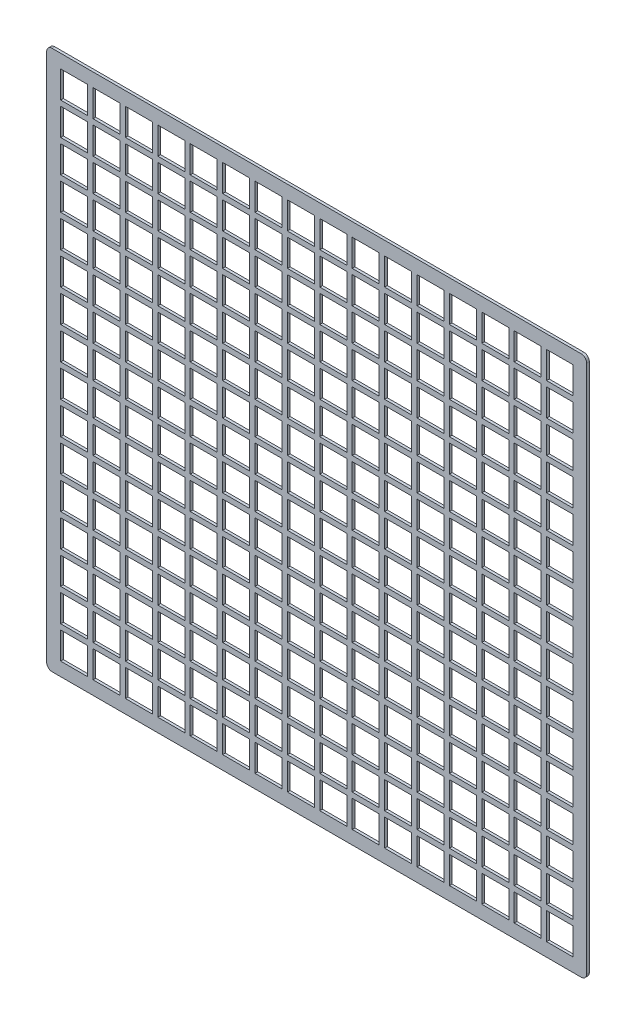
SolidWorks part; units mm, degrees
ref_plane "Front Plane" through (0, 0, 0) normal (0, 0, 1) x (1, 0, 0)
ref_plane "Top Plane" through (0, 0, 0) normal (0, 1, 0) x (1, 0, 0)
ref_plane "Right Plane" through (0, 0, 0) normal (1, 0, 0) x (0, 0, -1)
sketch "Model" plane through (0, 0, 0) normal (0, 0, 1) x (1, 0, 0)
  line L0 (0.1, 0) -> (9.9, 0)
  line L1 (10, 0.1) -> (10, 9.9)
  line L2 (9.9, 10) -> (0.1, 10)
  line L3 (0, 9.9) -> (0, 0.1)
  line L4 (0.2586, 0.25) -> (0.7586, 0.25)
  line L5 (0.7586, 0.25) -> (0.7586, 0.7491)
  line L6 (0.7586, 0.7491) -> (0.2586, 0.7491)
  line L7 (0.2586, 0.7491) -> (0.2586, 0.25)
  line L8 (0.2586, 0.8491) -> (0.7586, 0.8491)
  line L9 (0.7586, 0.8491) -> (0.7586, 1.3491)
  line L10 (0.7586, 1.3491) -> (0.2586, 1.3491)
  line L11 (0.2586, 1.3491) -> (0.2586, 0.8491)
  line L12 (0.2586, 1.4491) -> (0.7586, 1.4491)
  line L13 (0.7586, 1.4491) -> (0.7586, 1.9491)
  line L14 (0.7586, 1.9491) -> (0.2586, 1.9491)
  line L15 (0.2586, 1.9491) -> (0.2586, 1.4491)
  line L16 (0.2586, 2.0491) -> (0.7586, 2.0491)
  line L17 (0.7586, 2.0491) -> (0.7586, 2.5491)
  line L18 (0.7586, 2.5491) -> (0.2586, 2.5491)
  line L19 (0.2586, 2.5491) -> (0.2586, 2.0491)
  line L20 (0.2586, 2.6491) -> (0.7586, 2.6491)
  line L21 (0.7586, 2.6491) -> (0.7586, 3.1491)
  line L22 (0.7586, 3.1491) -> (0.2586, 3.1491)
  line L23 (0.2586, 3.1491) -> (0.2586, 2.6491)
  line L24 (0.2586, 3.2491) -> (0.7586, 3.2491)
  line L25 (0.7586, 3.2491) -> (0.7586, 3.7491)
  line L26 (0.7586, 3.7491) -> (0.2586, 3.7491)
  line L27 (0.2586, 3.7491) -> (0.2586, 3.2491)
  line L28 (0.2586, 3.8491) -> (0.7586, 3.8491)
  line L29 (0.7586, 3.8491) -> (0.7586, 4.3491)
  line L30 (0.7586, 4.3491) -> (0.2586, 4.3491)
  line L31 (0.2586, 4.3491) -> (0.2586, 3.8491)
  line L32 (0.2586, 4.4491) -> (0.7586, 4.4491)
  line L33 (0.7586, 4.4491) -> (0.7586, 4.9491)
  line L34 (0.7586, 4.9491) -> (0.2586, 4.9491)
  line L35 (0.2586, 4.9491) -> (0.2586, 4.4491)
  line L36 (0.2586, 5.0491) -> (0.7586, 5.0491)
  line L37 (0.7586, 5.0491) -> (0.7586, 5.5491)
  line L38 (0.7586, 5.5491) -> (0.2586, 5.5491)
  line L39 (0.2586, 5.5491) -> (0.2586, 5.0491)
  line L40 (0.2586, 5.6491) -> (0.7586, 5.6491)
  line L41 (0.7586, 5.6491) -> (0.7586, 6.1491)
  line L42 (0.7586, 6.1491) -> (0.2586, 6.1491)
  line L43 (0.2586, 6.1491) -> (0.2586, 5.6491)
  line L44 (0.2586, 6.2491) -> (0.7586, 6.2491)
  line L45 (0.7586, 6.2491) -> (0.7586, 6.7491)
  line L46 (0.7586, 6.7491) -> (0.2586, 6.7491)
  line L47 (0.2586, 6.7491) -> (0.2586, 6.2491)
  line L48 (0.2586, 6.8491) -> (0.7586, 6.8491)
  line L49 (0.7586, 6.8491) -> (0.7586, 7.3491)
  line L50 (0.7586, 7.3491) -> (0.2586, 7.3491)
  line L51 (0.2586, 7.3491) -> (0.2586, 6.8491)
  line L52 (0.2586, 7.4491) -> (0.7586, 7.4491)
  line L53 (0.7586, 7.4491) -> (0.7586, 7.9491)
  line L54 (0.7586, 7.9491) -> (0.2586, 7.9491)
  line L55 (0.2586, 7.9491) -> (0.2586, 7.4491)
  line L56 (0.2586, 8.0491) -> (0.7586, 8.0491)
  line L57 (0.7586, 8.0491) -> (0.7586, 8.5491)
  line L58 (0.7586, 8.5491) -> (0.2586, 8.5491)
  line L59 (0.2586, 8.5491) -> (0.2586, 8.0491)
  line L60 (0.2586, 8.6491) -> (0.7586, 8.6491)
  line L61 (0.7586, 8.6491) -> (0.7586, 9.1491)
  line L62 (0.7586, 9.1491) -> (0.2586, 9.1491)
  line L63 (0.2586, 9.1491) -> (0.2586, 8.6491)
  line L64 (0.2586, 9.2491) -> (0.7586, 9.2491)
  line L65 (0.7586, 9.2491) -> (0.7586, 9.7491)
  line L66 (0.7586, 9.7491) -> (0.2586, 9.7491)
  line L67 (0.2586, 9.7491) -> (0.2586, 9.2491)
  line L68 (1.3586, 0.25) -> (1.3586, 0.7491)
  line L69 (1.3586, 0.7491) -> (0.8586, 0.7491)
  line L70 (0.8586, 0.7491) -> (0.8586, 0.25)
  line L71 (0.8586, 0.8491) -> (1.3586, 0.8491)
  line L72 (1.3586, 0.8491) -> (1.3586, 1.3491)
  line L73 (1.3586, 1.3491) -> (0.8586, 1.3491)
  line L74 (0.8586, 1.3491) -> (0.8586, 0.8491)
  line L75 (0.8586, 1.4491) -> (1.3586, 1.4491)
  line L76 (1.3586, 1.4491) -> (1.3586, 1.9491)
  line L77 (1.3586, 1.9491) -> (0.8586, 1.9491)
  line L78 (0.8586, 1.9491) -> (0.8586, 1.4491)
  line L79 (0.8586, 2.0491) -> (1.3586, 2.0491)
  line L80 (1.3586, 2.0491) -> (1.3586, 2.5491)
  line L81 (1.3586, 2.5491) -> (0.8586, 2.5491)
  line L82 (0.8586, 2.5491) -> (0.8586, 2.0491)
  line L83 (0.8586, 2.6491) -> (1.3586, 2.6491)
  line L84 (1.3586, 2.6491) -> (1.3586, 3.1491)
  line L85 (1.3586, 3.1491) -> (0.8586, 3.1491)
  line L86 (0.8586, 3.1491) -> (0.8586, 2.6491)
  line L87 (0.8586, 3.2491) -> (1.3586, 3.2491)
  line L88 (1.3586, 3.2491) -> (1.3586, 3.7491)
  line L89 (1.3586, 3.7491) -> (0.8586, 3.7491)
  line L90 (0.8586, 3.7491) -> (0.8586, 3.2491)
  line L91 (0.8586, 3.8491) -> (1.3586, 3.8491)
  line L92 (1.3586, 3.8491) -> (1.3586, 4.3491)
  line L93 (1.3586, 4.3491) -> (0.8586, 4.3491)
  line L94 (0.8586, 4.3491) -> (0.8586, 3.8491)
  line L95 (0.8586, 4.4491) -> (1.3586, 4.4491)
  line L96 (1.3586, 4.4491) -> (1.3586, 4.9491)
  line L97 (1.3586, 4.9491) -> (0.8586, 4.9491)
  line L98 (0.8586, 4.9491) -> (0.8586, 4.4491)
  line L99 (0.8586, 5.0491) -> (1.3586, 5.0491)
  line L100 (1.3586, 5.0491) -> (1.3586, 5.5491)
  line L101 (1.3586, 5.5491) -> (0.8586, 5.5491)
  line L102 (0.8586, 5.5491) -> (0.8586, 5.0491)
  line L103 (0.8586, 5.6491) -> (1.3586, 5.6491)
  line L104 (1.3586, 5.6491) -> (1.3586, 6.1491)
  line L105 (1.3586, 6.1491) -> (0.8586, 6.1491)
  line L106 (0.8586, 6.1491) -> (0.8586, 5.6491)
  line L107 (0.8586, 6.2491) -> (1.3586, 6.2491)
  line L108 (1.3586, 6.2491) -> (1.3586, 6.7491)
  line L109 (1.3586, 6.7491) -> (0.8586, 6.7491)
  line L110 (0.8586, 6.7491) -> (0.8586, 6.2491)
  line L111 (0.8586, 6.8491) -> (1.3586, 6.8491)
  line L112 (1.3586, 6.8491) -> (1.3586, 7.3491)
  line L113 (1.3586, 7.3491) -> (0.8586, 7.3491)
  line L114 (0.8586, 7.3491) -> (0.8586, 6.8491)
  line L115 (0.8586, 7.4491) -> (1.3586, 7.4491)
  line L116 (1.3586, 7.4491) -> (1.3586, 7.9491)
  line L117 (1.3586, 7.9491) -> (0.8586, 7.9491)
  line L118 (0.8586, 7.9491) -> (0.8586, 7.4491)
  line L119 (0.8586, 8.0491) -> (1.3586, 8.0491)
  line L120 (1.3586, 8.0491) -> (1.3586, 8.5491)
  line L121 (1.3586, 8.5491) -> (0.8586, 8.5491)
  line L122 (0.8586, 8.5491) -> (0.8586, 8.0491)
  line L123 (0.8586, 8.6491) -> (1.3586, 8.6491)
  line L124 (1.3586, 8.6491) -> (1.3586, 9.1491)
  line L125 (1.3586, 9.1491) -> (0.8586, 9.1491)
  line L126 (0.8586, 9.1491) -> (0.8586, 8.6491)
  line L127 (0.8586, 9.2491) -> (1.3586, 9.2491)
  line L128 (1.3586, 9.2491) -> (1.3586, 9.7491)
  line L129 (1.3586, 9.7491) -> (0.8586, 9.7491)
  line L130 (0.8586, 9.7491) -> (0.8586, 9.2491)
  line L131 (1.9586, 0.25) -> (1.9586, 0.7491)
  line L132 (1.9586, 0.7491) -> (1.4586, 0.7491)
  line L133 (1.4586, 0.7491) -> (1.4586, 0.25)
  line L134 (1.4586, 0.8491) -> (1.9586, 0.8491)
  line L135 (1.9586, 0.8491) -> (1.9586, 1.3491)
  line L136 (1.9586, 1.3491) -> (1.4586, 1.3491)
  line L137 (1.4586, 1.3491) -> (1.4586, 0.8491)
  line L138 (1.4586, 1.4491) -> (1.9586, 1.4491)
  line L139 (1.9586, 1.4491) -> (1.9586, 1.9491)
  line L140 (1.9586, 1.9491) -> (1.4586, 1.9491)
  line L141 (1.4586, 1.9491) -> (1.4586, 1.4491)
  line L142 (1.4586, 2.0491) -> (1.9586, 2.0491)
  line L143 (1.9586, 2.0491) -> (1.9586, 2.5491)
  line L144 (1.9586, 2.5491) -> (1.4586, 2.5491)
  line L145 (1.4586, 2.5491) -> (1.4586, 2.0491)
  line L146 (1.4586, 2.6491) -> (1.9586, 2.6491)
  line L147 (1.9586, 2.6491) -> (1.9586, 3.1491)
  line L148 (1.9586, 3.1491) -> (1.4586, 3.1491)
  line L149 (1.4586, 3.1491) -> (1.4586, 2.6491)
  line L150 (1.4586, 3.2491) -> (1.9586, 3.2491)
  line L151 (1.9586, 3.2491) -> (1.9586, 3.7491)
  line L152 (1.9586, 3.7491) -> (1.4586, 3.7491)
  line L153 (1.4586, 3.7491) -> (1.4586, 3.2491)
  line L154 (1.4586, 3.8491) -> (1.9586, 3.8491)
  line L155 (1.9586, 3.8491) -> (1.9586, 4.3491)
  line L156 (1.9586, 4.3491) -> (1.4586, 4.3491)
  line L157 (1.4586, 4.3491) -> (1.4586, 3.8491)
  line L158 (1.4586, 4.4491) -> (1.9586, 4.4491)
  line L159 (1.9586, 4.4491) -> (1.9586, 4.9491)
  line L160 (1.9586, 4.9491) -> (1.4586, 4.9491)
  line L161 (1.4586, 4.9491) -> (1.4586, 4.4491)
  line L162 (1.4586, 5.0491) -> (1.9586, 5.0491)
  line L163 (1.9586, 5.0491) -> (1.9586, 5.5491)
  line L164 (1.9586, 5.5491) -> (1.4586, 5.5491)
  line L165 (1.4586, 5.5491) -> (1.4586, 5.0491)
  line L166 (1.4586, 5.6491) -> (1.9586, 5.6491)
  line L167 (1.9586, 5.6491) -> (1.9586, 6.1491)
  line L168 (1.9586, 6.1491) -> (1.4586, 6.1491)
  line L169 (1.4586, 6.1491) -> (1.4586, 5.6491)
  line L170 (1.4586, 6.2491) -> (1.9586, 6.2491)
  line L171 (1.9586, 6.2491) -> (1.9586, 6.7491)
  line L172 (1.9586, 6.7491) -> (1.4586, 6.7491)
  line L173 (1.4586, 6.7491) -> (1.4586, 6.2491)
  line L174 (1.4586, 6.8491) -> (1.9586, 6.8491)
  line L175 (1.9586, 6.8491) -> (1.9586, 7.3491)
  line L176 (1.9586, 7.3491) -> (1.4586, 7.3491)
  line L177 (1.4586, 7.3491) -> (1.4586, 6.8491)
  line L178 (1.4586, 7.4491) -> (1.9586, 7.4491)
  line L179 (1.9586, 7.4491) -> (1.9586, 7.9491)
  line L180 (1.9586, 7.9491) -> (1.4586, 7.9491)
  line L181 (1.4586, 7.9491) -> (1.4586, 7.4491)
  line L182 (1.4586, 8.0491) -> (1.9586, 8.0491)
  line L183 (1.9586, 8.0491) -> (1.9586, 8.5491)
  line L184 (1.9586, 8.5491) -> (1.4586, 8.5491)
  line L185 (1.4586, 8.5491) -> (1.4586, 8.0491)
  line L186 (1.4586, 8.6491) -> (1.9586, 8.6491)
  line L187 (1.9586, 8.6491) -> (1.9586, 9.1491)
  line L188 (1.9586, 9.1491) -> (1.4586, 9.1491)
  line L189 (1.4586, 9.1491) -> (1.4586, 8.6491)
  line L190 (1.4586, 9.2491) -> (1.9586, 9.2491)
  line L191 (1.9586, 9.2491) -> (1.9586, 9.7491)
  line L192 (1.9586, 9.7491) -> (1.4586, 9.7491)
  line L193 (1.4586, 9.7491) -> (1.4586, 9.2491)
  line L194 (2.5586, 0.25) -> (2.5586, 0.7491)
  line L195 (2.5586, 0.7491) -> (2.0586, 0.7491)
  line L196 (2.0586, 0.7491) -> (2.0586, 0.25)
  line L197 (2.0586, 0.8491) -> (2.5586, 0.8491)
  line L198 (2.5586, 0.8491) -> (2.5586, 1.3491)
  line L199 (2.5586, 1.3491) -> (2.0586, 1.3491)
  line L200 (2.0586, 1.3491) -> (2.0586, 0.8491)
  line L201 (2.0586, 1.4491) -> (2.5586, 1.4491)
  line L202 (2.5586, 1.4491) -> (2.5586, 1.9491)
  line L203 (2.5586, 1.9491) -> (2.0586, 1.9491)
  line L204 (2.0586, 1.9491) -> (2.0586, 1.4491)
  line L205 (2.0586, 2.0491) -> (2.5586, 2.0491)
  line L206 (2.5586, 2.0491) -> (2.5586, 2.5491)
  line L207 (2.5586, 2.5491) -> (2.0586, 2.5491)
  line L208 (2.0586, 2.5491) -> (2.0586, 2.0491)
  line L209 (2.0586, 2.6491) -> (2.5586, 2.6491)
  line L210 (2.5586, 2.6491) -> (2.5586, 3.1491)
  line L211 (2.5586, 3.1491) -> (2.0586, 3.1491)
  line L212 (2.0586, 3.1491) -> (2.0586, 2.6491)
  line L213 (2.0586, 3.2491) -> (2.5586, 3.2491)
  line L214 (2.5586, 3.2491) -> (2.5586, 3.7491)
  line L215 (2.5586, 3.7491) -> (2.0586, 3.7491)
  line L216 (2.0586, 3.7491) -> (2.0586, 3.2491)
  line L217 (2.0586, 3.8491) -> (2.5586, 3.8491)
  line L218 (2.5586, 3.8491) -> (2.5586, 4.3491)
  line L219 (2.5586, 4.3491) -> (2.0586, 4.3491)
  line L220 (2.0586, 4.3491) -> (2.0586, 3.8491)
  line L221 (2.0586, 4.4491) -> (2.5586, 4.4491)
  line L222 (2.5586, 4.4491) -> (2.5586, 4.9491)
  line L223 (2.5586, 4.9491) -> (2.0586, 4.9491)
  line L224 (2.0586, 4.9491) -> (2.0586, 4.4491)
  line L225 (2.0586, 5.0491) -> (2.5586, 5.0491)
  line L226 (2.5586, 5.0491) -> (2.5586, 5.5491)
  line L227 (2.5586, 5.5491) -> (2.0586, 5.5491)
  line L228 (2.0586, 5.5491) -> (2.0586, 5.0491)
  line L229 (2.0586, 5.6491) -> (2.5586, 5.6491)
  line L230 (2.5586, 5.6491) -> (2.5586, 6.1491)
  line L231 (2.5586, 6.1491) -> (2.0586, 6.1491)
  line L232 (2.0586, 6.1491) -> (2.0586, 5.6491)
  line L233 (2.0586, 6.2491) -> (2.5586, 6.2491)
  line L234 (2.5586, 6.2491) -> (2.5586, 6.7491)
  line L235 (2.5586, 6.7491) -> (2.0586, 6.7491)
  line L236 (2.0586, 6.7491) -> (2.0586, 6.2491)
  line L237 (2.0586, 6.8491) -> (2.5586, 6.8491)
  line L238 (2.5586, 6.8491) -> (2.5586, 7.3491)
  line L239 (2.5586, 7.3491) -> (2.0586, 7.3491)
  line L240 (2.0586, 7.3491) -> (2.0586, 6.8491)
  line L241 (2.0586, 7.4491) -> (2.5586, 7.4491)
  line L242 (2.5586, 7.4491) -> (2.5586, 7.9491)
  line L243 (2.5586, 7.9491) -> (2.0586, 7.9491)
  line L244 (2.0586, 7.9491) -> (2.0586, 7.4491)
  line L245 (2.0586, 8.0491) -> (2.5586, 8.0491)
  line L246 (2.5586, 8.0491) -> (2.5586, 8.5491)
  line L247 (2.5586, 8.5491) -> (2.0586, 8.5491)
  line L248 (2.0586, 8.5491) -> (2.0586, 8.0491)
  line L249 (2.0586, 8.6491) -> (2.5586, 8.6491)
  line L250 (2.5586, 8.6491) -> (2.5586, 9.1491)
  line L251 (2.5586, 9.1491) -> (2.0586, 9.1491)
  line L252 (2.0586, 9.1491) -> (2.0586, 8.6491)
  line L253 (2.0586, 9.2491) -> (2.5586, 9.2491)
  line L254 (2.5586, 9.2491) -> (2.5586, 9.7491)
  line L255 (2.5586, 9.7491) -> (2.0586, 9.7491)
  line L256 (2.0586, 9.7491) -> (2.0586, 9.2491)
  line L257 (3.1586, 0.25) -> (3.1586, 0.7491)
  line L258 (3.1586, 0.7491) -> (2.6586, 0.7491)
  line L259 (2.6586, 0.7491) -> (2.6586, 0.25)
  line L260 (2.6586, 0.8491) -> (3.1586, 0.8491)
  line L261 (3.1586, 0.8491) -> (3.1586, 1.3491)
  line L262 (3.1586, 1.3491) -> (2.6586, 1.3491)
  line L263 (2.6586, 1.3491) -> (2.6586, 0.8491)
  line L264 (2.6586, 1.4491) -> (3.1586, 1.4491)
  line L265 (3.1586, 1.4491) -> (3.1586, 1.9491)
  line L266 (3.1586, 1.9491) -> (2.6586, 1.9491)
  line L267 (2.6586, 1.9491) -> (2.6586, 1.4491)
  line L268 (2.6586, 2.0491) -> (3.1586, 2.0491)
  line L269 (3.1586, 2.0491) -> (3.1586, 2.5491)
  line L270 (3.1586, 2.5491) -> (2.6586, 2.5491)
  line L271 (2.6586, 2.5491) -> (2.6586, 2.0491)
  line L272 (2.6586, 2.6491) -> (3.1586, 2.6491)
  line L273 (3.1586, 2.6491) -> (3.1586, 3.1491)
  line L274 (3.1586, 3.1491) -> (2.6586, 3.1491)
  line L275 (2.6586, 3.1491) -> (2.6586, 2.6491)
  line L276 (2.6586, 3.2491) -> (3.1586, 3.2491)
  line L277 (3.1586, 3.2491) -> (3.1586, 3.7491)
  line L278 (3.1586, 3.7491) -> (2.6586, 3.7491)
  line L279 (2.6586, 3.7491) -> (2.6586, 3.2491)
  line L280 (2.6586, 3.8491) -> (3.1586, 3.8491)
  line L281 (3.1586, 3.8491) -> (3.1586, 4.3491)
  line L282 (3.1586, 4.3491) -> (2.6586, 4.3491)
  line L283 (2.6586, 4.3491) -> (2.6586, 3.8491)
  line L284 (2.6586, 4.4491) -> (3.1586, 4.4491)
  line L285 (3.1586, 4.4491) -> (3.1586, 4.9491)
  line L286 (3.1586, 4.9491) -> (2.6586, 4.9491)
  line L287 (2.6586, 4.9491) -> (2.6586, 4.4491)
  line L288 (2.6586, 5.0491) -> (3.1586, 5.0491)
  line L289 (3.1586, 5.0491) -> (3.1586, 5.5491)
  line L290 (3.1586, 5.5491) -> (2.6586, 5.5491)
  line L291 (2.6586, 5.5491) -> (2.6586, 5.0491)
  line L292 (2.6586, 5.6491) -> (3.1586, 5.6491)
  line L293 (3.1586, 5.6491) -> (3.1586, 6.1491)
  line L294 (3.1586, 6.1491) -> (2.6586, 6.1491)
  line L295 (2.6586, 6.1491) -> (2.6586, 5.6491)
  line L296 (2.6586, 6.2491) -> (3.1586, 6.2491)
  line L297 (3.1586, 6.2491) -> (3.1586, 6.7491)
  line L298 (3.1586, 6.7491) -> (2.6586, 6.7491)
  line L299 (2.6586, 6.7491) -> (2.6586, 6.2491)
  line L300 (2.6586, 6.8491) -> (3.1586, 6.8491)
  line L301 (3.1586, 6.8491) -> (3.1586, 7.3491)
  line L302 (3.1586, 7.3491) -> (2.6586, 7.3491)
  line L303 (2.6586, 7.3491) -> (2.6586, 6.8491)
  line L304 (2.6586, 7.4491) -> (3.1586, 7.4491)
  line L305 (3.1586, 7.4491) -> (3.1586, 7.9491)
  line L306 (3.1586, 7.9491) -> (2.6586, 7.9491)
  line L307 (2.6586, 7.9491) -> (2.6586, 7.4491)
  line L308 (2.6586, 8.0491) -> (3.1586, 8.0491)
  line L309 (3.1586, 8.0491) -> (3.1586, 8.5491)
  line L310 (3.1586, 8.5491) -> (2.6586, 8.5491)
  line L311 (2.6586, 8.5491) -> (2.6586, 8.0491)
  line L312 (2.6586, 8.6491) -> (3.1586, 8.6491)
  line L313 (3.1586, 8.6491) -> (3.1586, 9.1491)
  line L314 (3.1586, 9.1491) -> (2.6586, 9.1491)
  line L315 (2.6586, 9.1491) -> (2.6586, 8.6491)
  line L316 (2.6586, 9.2491) -> (3.1586, 9.2491)
  line L317 (3.1586, 9.2491) -> (3.1586, 9.7491)
  line L318 (3.1586, 9.7491) -> (2.6586, 9.7491)
  line L319 (2.6586, 9.7491) -> (2.6586, 9.2491)
  line L320 (3.7586, 0.25) -> (3.7586, 0.7491)
  line L321 (3.7586, 0.7491) -> (3.2586, 0.7491)
  line L322 (3.2586, 0.7491) -> (3.2586, 0.25)
  line L323 (3.2586, 0.8491) -> (3.7586, 0.8491)
  line L324 (3.7586, 0.8491) -> (3.7586, 1.3491)
  line L325 (3.7586, 1.3491) -> (3.2586, 1.3491)
  line L326 (3.2586, 1.3491) -> (3.2586, 0.8491)
  line L327 (3.2586, 1.4491) -> (3.7586, 1.4491)
  line L328 (3.7586, 1.4491) -> (3.7586, 1.9491)
  line L329 (3.7586, 1.9491) -> (3.2586, 1.9491)
  line L330 (3.2586, 1.9491) -> (3.2586, 1.4491)
  line L331 (3.2586, 2.0491) -> (3.7586, 2.0491)
  line L332 (3.7586, 2.0491) -> (3.7586, 2.5491)
  line L333 (3.7586, 2.5491) -> (3.2586, 2.5491)
  line L334 (3.2586, 2.5491) -> (3.2586, 2.0491)
  line L335 (3.2586, 2.6491) -> (3.7586, 2.6491)
  line L336 (3.7586, 2.6491) -> (3.7586, 3.1491)
  line L337 (3.7586, 3.1491) -> (3.2586, 3.1491)
  line L338 (3.2586, 3.1491) -> (3.2586, 2.6491)
  line L339 (3.2586, 3.2491) -> (3.7586, 3.2491)
  line L340 (3.7586, 3.2491) -> (3.7586, 3.7491)
  line L341 (3.7586, 3.7491) -> (3.2586, 3.7491)
  line L342 (3.2586, 3.7491) -> (3.2586, 3.2491)
  line L343 (3.2586, 3.8491) -> (3.7586, 3.8491)
  line L344 (3.7586, 3.8491) -> (3.7586, 4.3491)
  line L345 (3.7586, 4.3491) -> (3.2586, 4.3491)
  line L346 (3.2586, 4.3491) -> (3.2586, 3.8491)
  line L347 (3.2586, 4.4491) -> (3.7586, 4.4491)
  line L348 (3.7586, 4.4491) -> (3.7586, 4.9491)
  line L349 (3.7586, 4.9491) -> (3.2586, 4.9491)
  line L350 (3.2586, 4.9491) -> (3.2586, 4.4491)
  line L351 (3.2586, 5.0491) -> (3.7586, 5.0491)
  line L352 (3.7586, 5.0491) -> (3.7586, 5.5491)
  line L353 (3.7586, 5.5491) -> (3.2586, 5.5491)
  line L354 (3.2586, 5.5491) -> (3.2586, 5.0491)
  line L355 (3.2586, 5.6491) -> (3.7586, 5.6491)
  line L356 (3.7586, 5.6491) -> (3.7586, 6.1491)
  line L357 (3.7586, 6.1491) -> (3.2586, 6.1491)
  line L358 (3.2586, 6.1491) -> (3.2586, 5.6491)
  line L359 (3.2586, 6.2491) -> (3.7586, 6.2491)
  line L360 (3.7586, 6.2491) -> (3.7586, 6.7491)
  line L361 (3.7586, 6.7491) -> (3.2586, 6.7491)
  line L362 (3.2586, 6.7491) -> (3.2586, 6.2491)
  line L363 (3.2586, 6.8491) -> (3.7586, 6.8491)
  line L364 (3.7586, 6.8491) -> (3.7586, 7.3491)
  line L365 (3.7586, 7.3491) -> (3.2586, 7.3491)
  line L366 (3.2586, 7.3491) -> (3.2586, 6.8491)
  line L367 (3.2586, 7.4491) -> (3.7586, 7.4491)
  line L368 (3.7586, 7.4491) -> (3.7586, 7.9491)
  line L369 (3.7586, 7.9491) -> (3.2586, 7.9491)
  line L370 (3.2586, 7.9491) -> (3.2586, 7.4491)
  line L371 (3.2586, 8.0491) -> (3.7586, 8.0491)
  line L372 (3.7586, 8.0491) -> (3.7586, 8.5491)
  line L373 (3.7586, 8.5491) -> (3.2586, 8.5491)
  line L374 (3.2586, 8.5491) -> (3.2586, 8.0491)
  line L375 (3.2586, 8.6491) -> (3.7586, 8.6491)
  line L376 (3.7586, 8.6491) -> (3.7586, 9.1491)
  line L377 (3.7586, 9.1491) -> (3.2586, 9.1491)
  line L378 (3.2586, 9.1491) -> (3.2586, 8.6491)
  line L379 (3.2586, 9.2491) -> (3.7586, 9.2491)
  line L380 (3.7586, 9.2491) -> (3.7586, 9.7491)
  line L381 (3.7586, 9.7491) -> (3.2586, 9.7491)
  line L382 (3.2586, 9.7491) -> (3.2586, 9.2491)
  line L383 (4.3586, 0.25) -> (4.3586, 0.7491)
  line L384 (4.3586, 0.7491) -> (3.8586, 0.7491)
  line L385 (3.8586, 0.7491) -> (3.8586, 0.25)
  line L386 (3.8586, 0.8491) -> (4.3586, 0.8491)
  line L387 (4.3586, 0.8491) -> (4.3586, 1.3491)
  line L388 (4.3586, 1.3491) -> (3.8586, 1.3491)
  line L389 (3.8586, 1.3491) -> (3.8586, 0.8491)
  line L390 (3.8586, 1.4491) -> (4.3586, 1.4491)
  line L391 (4.3586, 1.4491) -> (4.3586, 1.9491)
  line L392 (4.3586, 1.9491) -> (3.8586, 1.9491)
  line L393 (3.8586, 1.9491) -> (3.8586, 1.4491)
  line L394 (3.8586, 2.0491) -> (4.3586, 2.0491)
  line L395 (4.3586, 2.0491) -> (4.3586, 2.5491)
  line L396 (4.3586, 2.5491) -> (3.8586, 2.5491)
  line L397 (3.8586, 2.5491) -> (3.8586, 2.0491)
  line L398 (3.8586, 2.6491) -> (4.3586, 2.6491)
  line L399 (4.3586, 2.6491) -> (4.3586, 3.1491)
  line L400 (4.3586, 3.1491) -> (3.8586, 3.1491)
  line L401 (3.8586, 3.1491) -> (3.8586, 2.6491)
  line L402 (3.8586, 3.2491) -> (4.3586, 3.2491)
  line L403 (4.3586, 3.2491) -> (4.3586, 3.7491)
  line L404 (4.3586, 3.7491) -> (3.8586, 3.7491)
  line L405 (3.8586, 3.7491) -> (3.8586, 3.2491)
  line L406 (3.8586, 3.8491) -> (4.3586, 3.8491)
  line L407 (4.3586, 3.8491) -> (4.3586, 4.3491)
  line L408 (4.3586, 4.3491) -> (3.8586, 4.3491)
  line L409 (3.8586, 4.3491) -> (3.8586, 3.8491)
  line L410 (3.8586, 4.4491) -> (4.3586, 4.4491)
  line L411 (4.3586, 4.4491) -> (4.3586, 4.9491)
  line L412 (4.3586, 4.9491) -> (3.8586, 4.9491)
  line L413 (3.8586, 4.9491) -> (3.8586, 4.4491)
  line L414 (3.8586, 5.0491) -> (4.3586, 5.0491)
  line L415 (4.3586, 5.0491) -> (4.3586, 5.5491)
  line L416 (4.3586, 5.5491) -> (3.8586, 5.5491)
  line L417 (3.8586, 5.5491) -> (3.8586, 5.0491)
  line L418 (3.8586, 5.6491) -> (4.3586, 5.6491)
  line L419 (4.3586, 5.6491) -> (4.3586, 6.1491)
  line L420 (4.3586, 6.1491) -> (3.8586, 6.1491)
  line L421 (3.8586, 6.1491) -> (3.8586, 5.6491)
  line L422 (3.8586, 6.2491) -> (4.3586, 6.2491)
  line L423 (4.3586, 6.2491) -> (4.3586, 6.7491)
  line L424 (4.3586, 6.7491) -> (3.8586, 6.7491)
  line L425 (3.8586, 6.7491) -> (3.8586, 6.2491)
  line L426 (3.8586, 6.8491) -> (4.3586, 6.8491)
  line L427 (4.3586, 6.8491) -> (4.3586, 7.3491)
  line L428 (4.3586, 7.3491) -> (3.8586, 7.3491)
  line L429 (3.8586, 7.3491) -> (3.8586, 6.8491)
  line L430 (3.8586, 7.4491) -> (4.3586, 7.4491)
  line L431 (4.3586, 7.4491) -> (4.3586, 7.9491)
  line L432 (4.3586, 7.9491) -> (3.8586, 7.9491)
  line L433 (3.8586, 7.9491) -> (3.8586, 7.4491)
  line L434 (3.8586, 8.0491) -> (4.3586, 8.0491)
  line L435 (4.3586, 8.0491) -> (4.3586, 8.5491)
  line L436 (4.3586, 8.5491) -> (3.8586, 8.5491)
  line L437 (3.8586, 8.5491) -> (3.8586, 8.0491)
  line L438 (3.8586, 8.6491) -> (4.3586, 8.6491)
  line L439 (4.3586, 8.6491) -> (4.3586, 9.1491)
  line L440 (4.3586, 9.1491) -> (3.8586, 9.1491)
  line L441 (3.8586, 9.1491) -> (3.8586, 8.6491)
  line L442 (3.8586, 9.2491) -> (4.3586, 9.2491)
  line L443 (4.3586, 9.2491) -> (4.3586, 9.7491)
  line L444 (4.3586, 9.7491) -> (3.8586, 9.7491)
  line L445 (3.8586, 9.7491) -> (3.8586, 9.2491)
  line L446 (4.9586, 0.25) -> (4.9586, 0.7491)
  line L447 (4.9586, 0.7491) -> (4.4586, 0.7491)
  line L448 (4.4586, 0.7491) -> (4.4586, 0.25)
  line L449 (4.4586, 0.8491) -> (4.9586, 0.8491)
  line L450 (4.9586, 0.8491) -> (4.9586, 1.3491)
  line L451 (4.9586, 1.3491) -> (4.4586, 1.3491)
  line L452 (4.4586, 1.3491) -> (4.4586, 0.8491)
  line L453 (4.4586, 1.4491) -> (4.9586, 1.4491)
  line L454 (4.9586, 1.4491) -> (4.9586, 1.9491)
  line L455 (4.9586, 1.9491) -> (4.4586, 1.9491)
  line L456 (4.4586, 1.9491) -> (4.4586, 1.4491)
  line L457 (4.4586, 2.0491) -> (4.9586, 2.0491)
  line L458 (4.9586, 2.0491) -> (4.9586, 2.5491)
  line L459 (4.9586, 2.5491) -> (4.4586, 2.5491)
  line L460 (4.4586, 2.5491) -> (4.4586, 2.0491)
  line L461 (4.4586, 2.6491) -> (4.9586, 2.6491)
  line L462 (4.9586, 2.6491) -> (4.9586, 3.1491)
  line L463 (4.9586, 3.1491) -> (4.4586, 3.1491)
  line L464 (4.4586, 3.1491) -> (4.4586, 2.6491)
  line L465 (4.4586, 3.2491) -> (4.9586, 3.2491)
  line L466 (4.9586, 3.2491) -> (4.9586, 3.7491)
  line L467 (4.9586, 3.7491) -> (4.4586, 3.7491)
  line L468 (4.4586, 3.7491) -> (4.4586, 3.2491)
  line L469 (4.4586, 3.8491) -> (4.9586, 3.8491)
  line L470 (4.9586, 3.8491) -> (4.9586, 4.3491)
  line L471 (4.9586, 4.3491) -> (4.4586, 4.3491)
  line L472 (4.4586, 4.3491) -> (4.4586, 3.8491)
  line L473 (4.4586, 4.4491) -> (4.9586, 4.4491)
  line L474 (4.9586, 4.4491) -> (4.9586, 4.9491)
  line L475 (4.9586, 4.9491) -> (4.4586, 4.9491)
  line L476 (4.4586, 4.9491) -> (4.4586, 4.4491)
  line L477 (4.4586, 5.0491) -> (4.9586, 5.0491)
  line L478 (4.9586, 5.0491) -> (4.9586, 5.5491)
  line L479 (4.9586, 5.5491) -> (4.4586, 5.5491)
  line L480 (4.4586, 5.5491) -> (4.4586, 5.0491)
  line L481 (4.4586, 5.6491) -> (4.9586, 5.6491)
  line L482 (4.9586, 5.6491) -> (4.9586, 6.1491)
  line L483 (4.9586, 6.1491) -> (4.4586, 6.1491)
  line L484 (4.4586, 6.1491) -> (4.4586, 5.6491)
  line L485 (4.4586, 6.2491) -> (4.9586, 6.2491)
  line L486 (4.9586, 6.2491) -> (4.9586, 6.7491)
  line L487 (4.9586, 6.7491) -> (4.4586, 6.7491)
  line L488 (4.4586, 6.7491) -> (4.4586, 6.2491)
  line L489 (4.4586, 6.8491) -> (4.9586, 6.8491)
  line L490 (4.9586, 6.8491) -> (4.9586, 7.3491)
  line L491 (4.9586, 7.3491) -> (4.4586, 7.3491)
  line L492 (4.4586, 7.3491) -> (4.4586, 6.8491)
  line L493 (4.4586, 7.4491) -> (4.9586, 7.4491)
  line L494 (4.9586, 7.4491) -> (4.9586, 7.9491)
  line L495 (4.9586, 7.9491) -> (4.4586, 7.9491)
  line L496 (4.4586, 7.9491) -> (4.4586, 7.4491)
  line L497 (4.4586, 8.0491) -> (4.9586, 8.0491)
  line L498 (4.9586, 8.0491) -> (4.9586, 8.5491)
  line L499 (4.9586, 8.5491) -> (4.4586, 8.5491)
  line L500 (4.4586, 8.5491) -> (4.4586, 8.0491)
  line L501 (4.4586, 8.6491) -> (4.9586, 8.6491)
  line L502 (4.9586, 8.6491) -> (4.9586, 9.1491)
  line L503 (4.9586, 9.1491) -> (4.4586, 9.1491)
  line L504 (4.4586, 9.1491) -> (4.4586, 8.6491)
  line L505 (4.4586, 9.2491) -> (4.9586, 9.2491)
  line L506 (4.9586, 9.2491) -> (4.9586, 9.7491)
  line L507 (4.9586, 9.7491) -> (4.4586, 9.7491)
  line L508 (4.4586, 9.7491) -> (4.4586, 9.2491)
  line L509 (5.5586, 0.25) -> (5.5586, 0.7491)
  line L510 (5.5586, 0.7491) -> (5.0586, 0.7491)
  line L511 (5.0586, 0.7491) -> (5.0586, 0.25)
  line L512 (5.0586, 0.8491) -> (5.5586, 0.8491)
  line L513 (5.5586, 0.8491) -> (5.5586, 1.3491)
  line L514 (5.5586, 1.3491) -> (5.0586, 1.3491)
  line L515 (5.0586, 1.3491) -> (5.0586, 0.8491)
  line L516 (5.0586, 1.4491) -> (5.5586, 1.4491)
  line L517 (5.5586, 1.4491) -> (5.5586, 1.9491)
  line L518 (5.5586, 1.9491) -> (5.0586, 1.9491)
  line L519 (5.0586, 1.9491) -> (5.0586, 1.4491)
  line L520 (5.0586, 2.0491) -> (5.5586, 2.0491)
  line L521 (5.5586, 2.0491) -> (5.5586, 2.5491)
  line L522 (5.5586, 2.5491) -> (5.0586, 2.5491)
  line L523 (5.0586, 2.5491) -> (5.0586, 2.0491)
  line L524 (5.0586, 2.6491) -> (5.5586, 2.6491)
  line L525 (5.5586, 2.6491) -> (5.5586, 3.1491)
  line L526 (5.5586, 3.1491) -> (5.0586, 3.1491)
  line L527 (5.0586, 3.1491) -> (5.0586, 2.6491)
  line L528 (5.0586, 3.2491) -> (5.5586, 3.2491)
  line L529 (5.5586, 3.2491) -> (5.5586, 3.7491)
  line L530 (5.5586, 3.7491) -> (5.0586, 3.7491)
  line L531 (5.0586, 3.7491) -> (5.0586, 3.2491)
  line L532 (5.0586, 3.8491) -> (5.5586, 3.8491)
  line L533 (5.5586, 3.8491) -> (5.5586, 4.3491)
  line L534 (5.5586, 4.3491) -> (5.0586, 4.3491)
  line L535 (5.0586, 4.3491) -> (5.0586, 3.8491)
  line L536 (5.0586, 4.4491) -> (5.5586, 4.4491)
  line L537 (5.5586, 4.4491) -> (5.5586, 4.9491)
  line L538 (5.5586, 4.9491) -> (5.0586, 4.9491)
  line L539 (5.0586, 4.9491) -> (5.0586, 4.4491)
  line L540 (5.0586, 5.0491) -> (5.5586, 5.0491)
  line L541 (5.5586, 5.0491) -> (5.5586, 5.5491)
  line L542 (5.5586, 5.5491) -> (5.0586, 5.5491)
  line L543 (5.0586, 5.5491) -> (5.0586, 5.0491)
  line L544 (5.0586, 5.6491) -> (5.5586, 5.6491)
  line L545 (5.5586, 5.6491) -> (5.5586, 6.1491)
  line L546 (5.5586, 6.1491) -> (5.0586, 6.1491)
  line L547 (5.0586, 6.1491) -> (5.0586, 5.6491)
  line L548 (5.0586, 6.2491) -> (5.5586, 6.2491)
  line L549 (5.5586, 6.2491) -> (5.5586, 6.7491)
  line L550 (5.5586, 6.7491) -> (5.0586, 6.7491)
  line L551 (5.0586, 6.7491) -> (5.0586, 6.2491)
  line L552 (5.0586, 6.8491) -> (5.5586, 6.8491)
  line L553 (5.5586, 6.8491) -> (5.5586, 7.3491)
  line L554 (5.5586, 7.3491) -> (5.0586, 7.3491)
  line L555 (5.0586, 7.3491) -> (5.0586, 6.8491)
  line L556 (5.0586, 7.4491) -> (5.5586, 7.4491)
  line L557 (5.5586, 7.4491) -> (5.5586, 7.9491)
  line L558 (5.5586, 7.9491) -> (5.0586, 7.9491)
  line L559 (5.0586, 7.9491) -> (5.0586, 7.4491)
  line L560 (5.0586, 8.0491) -> (5.5586, 8.0491)
  line L561 (5.5586, 8.0491) -> (5.5586, 8.5491)
  line L562 (5.5586, 8.5491) -> (5.0586, 8.5491)
  line L563 (5.0586, 8.5491) -> (5.0586, 8.0491)
  line L564 (5.0586, 8.6491) -> (5.5586, 8.6491)
  line L565 (5.5586, 8.6491) -> (5.5586, 9.1491)
  line L566 (5.5586, 9.1491) -> (5.0586, 9.1491)
  line L567 (5.0586, 9.1491) -> (5.0586, 8.6491)
  line L568 (5.0586, 9.2491) -> (5.5586, 9.2491)
  line L569 (5.5586, 9.2491) -> (5.5586, 9.7491)
  line L570 (5.5586, 9.7491) -> (5.0586, 9.7491)
  line L571 (5.0586, 9.7491) -> (5.0586, 9.2491)
  line L572 (6.1586, 0.25) -> (6.1586, 0.7491)
  line L573 (6.1586, 0.7491) -> (5.6586, 0.7491)
  line L574 (5.6586, 0.7491) -> (5.6586, 0.25)
  line L575 (5.6586, 0.8491) -> (6.1586, 0.8491)
  line L576 (6.1586, 0.8491) -> (6.1586, 1.3491)
  line L577 (6.1586, 1.3491) -> (5.6586, 1.3491)
  line L578 (5.6586, 1.3491) -> (5.6586, 0.8491)
  line L579 (5.6586, 1.4491) -> (6.1586, 1.4491)
  line L580 (6.1586, 1.4491) -> (6.1586, 1.9491)
  line L581 (6.1586, 1.9491) -> (5.6586, 1.9491)
  line L582 (5.6586, 1.9491) -> (5.6586, 1.4491)
  line L583 (5.6586, 2.0491) -> (6.1586, 2.0491)
  line L584 (6.1586, 2.0491) -> (6.1586, 2.5491)
  line L585 (6.1586, 2.5491) -> (5.6586, 2.5491)
  line L586 (5.6586, 2.5491) -> (5.6586, 2.0491)
  line L587 (5.6586, 2.6491) -> (6.1586, 2.6491)
  line L588 (6.1586, 2.6491) -> (6.1586, 3.1491)
  line L589 (6.1586, 3.1491) -> (5.6586, 3.1491)
  line L590 (5.6586, 3.1491) -> (5.6586, 2.6491)
  line L591 (5.6586, 3.2491) -> (6.1586, 3.2491)
  line L592 (6.1586, 3.2491) -> (6.1586, 3.7491)
  line L593 (6.1586, 3.7491) -> (5.6586, 3.7491)
  line L594 (5.6586, 3.7491) -> (5.6586, 3.2491)
  line L595 (5.6586, 3.8491) -> (6.1586, 3.8491)
  line L596 (6.1586, 3.8491) -> (6.1586, 4.3491)
  line L597 (6.1586, 4.3491) -> (5.6586, 4.3491)
  line L598 (5.6586, 4.3491) -> (5.6586, 3.8491)
  line L599 (5.6586, 4.4491) -> (6.1586, 4.4491)
  line L600 (6.1586, 4.4491) -> (6.1586, 4.9491)
  line L601 (6.1586, 4.9491) -> (5.6586, 4.9491)
  line L602 (5.6586, 4.9491) -> (5.6586, 4.4491)
  line L603 (5.6586, 5.0491) -> (6.1586, 5.0491)
  line L604 (6.1586, 5.0491) -> (6.1586, 5.5491)
  line L605 (6.1586, 5.5491) -> (5.6586, 5.5491)
  line L606 (5.6586, 5.5491) -> (5.6586, 5.0491)
  line L607 (5.6586, 5.6491) -> (6.1586, 5.6491)
  line L608 (6.1586, 5.6491) -> (6.1586, 6.1491)
  line L609 (6.1586, 6.1491) -> (5.6586, 6.1491)
  line L610 (5.6586, 6.1491) -> (5.6586, 5.6491)
  line L611 (5.6586, 6.2491) -> (6.1586, 6.2491)
  line L612 (6.1586, 6.2491) -> (6.1586, 6.7491)
  line L613 (6.1586, 6.7491) -> (5.6586, 6.7491)
  line L614 (5.6586, 6.7491) -> (5.6586, 6.2491)
  line L615 (5.6586, 6.8491) -> (6.1586, 6.8491)
  line L616 (6.1586, 6.8491) -> (6.1586, 7.3491)
  line L617 (6.1586, 7.3491) -> (5.6586, 7.3491)
  line L618 (5.6586, 7.3491) -> (5.6586, 6.8491)
  line L619 (5.6586, 7.4491) -> (6.1586, 7.4491)
  line L620 (6.1586, 7.4491) -> (6.1586, 7.9491)
  line L621 (6.1586, 7.9491) -> (5.6586, 7.9491)
  line L622 (5.6586, 7.9491) -> (5.6586, 7.4491)
  line L623 (5.6586, 8.0491) -> (6.1586, 8.0491)
  line L624 (6.1586, 8.0491) -> (6.1586, 8.5491)
  line L625 (6.1586, 8.5491) -> (5.6586, 8.5491)
  line L626 (5.6586, 8.5491) -> (5.6586, 8.0491)
  line L627 (5.6586, 8.6491) -> (6.1586, 8.6491)
  line L628 (6.1586, 8.6491) -> (6.1586, 9.1491)
  line L629 (6.1586, 9.1491) -> (5.6586, 9.1491)
  line L630 (5.6586, 9.1491) -> (5.6586, 8.6491)
  line L631 (5.6586, 9.2491) -> (6.1586, 9.2491)
  line L632 (6.1586, 9.2491) -> (6.1586, 9.7491)
  line L633 (6.1586, 9.7491) -> (5.6586, 9.7491)
  line L634 (5.6586, 9.7491) -> (5.6586, 9.2491)
  line L635 (6.7586, 0.25) -> (6.7586, 0.7491)
  line L636 (6.7586, 0.7491) -> (6.2586, 0.7491)
  line L637 (6.2586, 0.7491) -> (6.2586, 0.25)
  line L638 (6.2586, 0.8491) -> (6.7586, 0.8491)
  line L639 (6.7586, 0.8491) -> (6.7586, 1.3491)
  line L640 (6.7586, 1.3491) -> (6.2586, 1.3491)
  line L641 (6.2586, 1.3491) -> (6.2586, 0.8491)
  line L642 (6.2586, 1.4491) -> (6.7586, 1.4491)
  line L643 (6.7586, 1.4491) -> (6.7586, 1.9491)
  line L644 (6.7586, 1.9491) -> (6.2586, 1.9491)
  line L645 (6.2586, 1.9491) -> (6.2586, 1.4491)
  line L646 (6.2586, 2.0491) -> (6.7586, 2.0491)
  line L647 (6.7586, 2.0491) -> (6.7586, 2.5491)
  line L648 (6.7586, 2.5491) -> (6.2586, 2.5491)
  line L649 (6.2586, 2.5491) -> (6.2586, 2.0491)
  line L650 (6.2586, 2.6491) -> (6.7586, 2.6491)
  line L651 (6.7586, 2.6491) -> (6.7586, 3.1491)
  line L652 (6.7586, 3.1491) -> (6.2586, 3.1491)
  line L653 (6.2586, 3.1491) -> (6.2586, 2.6491)
  line L654 (6.2586, 3.2491) -> (6.7586, 3.2491)
  line L655 (6.7586, 3.2491) -> (6.7586, 3.7491)
  line L656 (6.7586, 3.7491) -> (6.2586, 3.7491)
  line L657 (6.2586, 3.7491) -> (6.2586, 3.2491)
  line L658 (6.2586, 3.8491) -> (6.7586, 3.8491)
  line L659 (6.7586, 3.8491) -> (6.7586, 4.3491)
  line L660 (6.7586, 4.3491) -> (6.2586, 4.3491)
  line L661 (6.2586, 4.3491) -> (6.2586, 3.8491)
  line L662 (6.2586, 4.4491) -> (6.7586, 4.4491)
  line L663 (6.7586, 4.4491) -> (6.7586, 4.9491)
  line L664 (6.7586, 4.9491) -> (6.2586, 4.9491)
  line L665 (6.2586, 4.9491) -> (6.2586, 4.4491)
  line L666 (6.2586, 5.0491) -> (6.7586, 5.0491)
  line L667 (6.7586, 5.0491) -> (6.7586, 5.5491)
  line L668 (6.7586, 5.5491) -> (6.2586, 5.5491)
  line L669 (6.2586, 5.5491) -> (6.2586, 5.0491)
  line L670 (6.2586, 5.6491) -> (6.7586, 5.6491)
  line L671 (6.7586, 5.6491) -> (6.7586, 6.1491)
  line L672 (6.7586, 6.1491) -> (6.2586, 6.1491)
  line L673 (6.2586, 6.1491) -> (6.2586, 5.6491)
  line L674 (6.2586, 6.2491) -> (6.7586, 6.2491)
  line L675 (6.7586, 6.2491) -> (6.7586, 6.7491)
  line L676 (6.7586, 6.7491) -> (6.2586, 6.7491)
  line L677 (6.2586, 6.7491) -> (6.2586, 6.2491)
  line L678 (6.2586, 6.8491) -> (6.7586, 6.8491)
  line L679 (6.7586, 6.8491) -> (6.7586, 7.3491)
  line L680 (6.7586, 7.3491) -> (6.2586, 7.3491)
  line L681 (6.2586, 7.3491) -> (6.2586, 6.8491)
  line L682 (6.2586, 7.4491) -> (6.7586, 7.4491)
  line L683 (6.7586, 7.4491) -> (6.7586, 7.9491)
  line L684 (6.7586, 7.9491) -> (6.2586, 7.9491)
  line L685 (6.2586, 7.9491) -> (6.2586, 7.4491)
  line L686 (6.2586, 8.0491) -> (6.7586, 8.0491)
  line L687 (6.7586, 8.0491) -> (6.7586, 8.5491)
  line L688 (6.7586, 8.5491) -> (6.2586, 8.5491)
  line L689 (6.2586, 8.5491) -> (6.2586, 8.0491)
  line L690 (6.2586, 8.6491) -> (6.7586, 8.6491)
  line L691 (6.7586, 8.6491) -> (6.7586, 9.1491)
  line L692 (6.7586, 9.1491) -> (6.2586, 9.1491)
  line L693 (6.2586, 9.1491) -> (6.2586, 8.6491)
  line L694 (6.2586, 9.2491) -> (6.7586, 9.2491)
  line L695 (6.7586, 9.2491) -> (6.7586, 9.7491)
  line L696 (6.7586, 9.7491) -> (6.2586, 9.7491)
  line L697 (6.2586, 9.7491) -> (6.2586, 9.2491)
  line L698 (7.3586, 0.25) -> (7.3586, 0.7491)
  line L699 (7.3586, 0.7491) -> (6.8586, 0.7491)
  line L700 (6.8586, 0.7491) -> (6.8586, 0.25)
  line L701 (6.8586, 0.8491) -> (7.3586, 0.8491)
  line L702 (7.3586, 0.8491) -> (7.3586, 1.3491)
  line L703 (7.3586, 1.3491) -> (6.8586, 1.3491)
  line L704 (6.8586, 1.3491) -> (6.8586, 0.8491)
  line L705 (6.8586, 1.4491) -> (7.3586, 1.4491)
  line L706 (7.3586, 1.4491) -> (7.3586, 1.9491)
  line L707 (7.3586, 1.9491) -> (6.8586, 1.9491)
  line L708 (6.8586, 1.9491) -> (6.8586, 1.4491)
  line L709 (6.8586, 2.0491) -> (7.3586, 2.0491)
  line L710 (7.3586, 2.0491) -> (7.3586, 2.5491)
  line L711 (7.3586, 2.5491) -> (6.8586, 2.5491)
  line L712 (6.8586, 2.5491) -> (6.8586, 2.0491)
  line L713 (6.8586, 2.6491) -> (7.3586, 2.6491)
  line L714 (7.3586, 2.6491) -> (7.3586, 3.1491)
  line L715 (7.3586, 3.1491) -> (6.8586, 3.1491)
  line L716 (6.8586, 3.1491) -> (6.8586, 2.6491)
  line L717 (6.8586, 3.2491) -> (7.3586, 3.2491)
  line L718 (7.3586, 3.2491) -> (7.3586, 3.7491)
  line L719 (7.3586, 3.7491) -> (6.8586, 3.7491)
  line L720 (6.8586, 3.7491) -> (6.8586, 3.2491)
  line L721 (6.8586, 3.8491) -> (7.3586, 3.8491)
  line L722 (7.3586, 3.8491) -> (7.3586, 4.3491)
  line L723 (7.3586, 4.3491) -> (6.8586, 4.3491)
  line L724 (6.8586, 4.3491) -> (6.8586, 3.8491)
  line L725 (6.8586, 4.4491) -> (7.3586, 4.4491)
  line L726 (7.3586, 4.4491) -> (7.3586, 4.9491)
  line L727 (7.3586, 4.9491) -> (6.8586, 4.9491)
  line L728 (6.8586, 4.9491) -> (6.8586, 4.4491)
  line L729 (6.8586, 5.0491) -> (7.3586, 5.0491)
  line L730 (7.3586, 5.0491) -> (7.3586, 5.5491)
  line L731 (7.3586, 5.5491) -> (6.8586, 5.5491)
  line L732 (6.8586, 5.5491) -> (6.8586, 5.0491)
  line L733 (6.8586, 5.6491) -> (7.3586, 5.6491)
  line L734 (7.3586, 5.6491) -> (7.3586, 6.1491)
  line L735 (7.3586, 6.1491) -> (6.8586, 6.1491)
  line L736 (6.8586, 6.1491) -> (6.8586, 5.6491)
  line L737 (6.8586, 6.2491) -> (7.3586, 6.2491)
  line L738 (7.3586, 6.2491) -> (7.3586, 6.7491)
  line L739 (7.3586, 6.7491) -> (6.8586, 6.7491)
  line L740 (6.8586, 6.7491) -> (6.8586, 6.2491)
  line L741 (6.8586, 6.8491) -> (7.3586, 6.8491)
  line L742 (7.3586, 6.8491) -> (7.3586, 7.3491)
  line L743 (7.3586, 7.3491) -> (6.8586, 7.3491)
  line L744 (6.8586, 7.3491) -> (6.8586, 6.8491)
  line L745 (6.8586, 7.4491) -> (7.3586, 7.4491)
  line L746 (7.3586, 7.4491) -> (7.3586, 7.9491)
  line L747 (7.3586, 7.9491) -> (6.8586, 7.9491)
  line L748 (6.8586, 7.9491) -> (6.8586, 7.4491)
  line L749 (6.8586, 8.0491) -> (7.3586, 8.0491)
  line L750 (7.3586, 8.0491) -> (7.3586, 8.5491)
  line L751 (7.3586, 8.5491) -> (6.8586, 8.5491)
  line L752 (6.8586, 8.5491) -> (6.8586, 8.0491)
  line L753 (6.8586, 8.6491) -> (7.3586, 8.6491)
  line L754 (7.3586, 8.6491) -> (7.3586, 9.1491)
  line L755 (7.3586, 9.1491) -> (6.8586, 9.1491)
  line L756 (6.8586, 9.1491) -> (6.8586, 8.6491)
  line L757 (6.8586, 9.2491) -> (7.3586, 9.2491)
  line L758 (7.3586, 9.2491) -> (7.3586, 9.7491)
  line L759 (7.3586, 9.7491) -> (6.8586, 9.7491)
  line L760 (6.8586, 9.7491) -> (6.8586, 9.2491)
  line L761 (7.9586, 0.25) -> (7.9586, 0.7491)
  line L762 (7.9586, 0.7491) -> (7.4586, 0.7491)
  line L763 (7.4586, 0.7491) -> (7.4586, 0.25)
  line L764 (7.4586, 0.8491) -> (7.9586, 0.8491)
  line L765 (7.9586, 0.8491) -> (7.9586, 1.3491)
  line L766 (7.9586, 1.3491) -> (7.4586, 1.3491)
  line L767 (7.4586, 1.3491) -> (7.4586, 0.8491)
  line L768 (7.4586, 1.4491) -> (7.9586, 1.4491)
  line L769 (7.9586, 1.4491) -> (7.9586, 1.9491)
  line L770 (7.9586, 1.9491) -> (7.4586, 1.9491)
  line L771 (7.4586, 1.9491) -> (7.4586, 1.4491)
  line L772 (7.4586, 2.0491) -> (7.9586, 2.0491)
  line L773 (7.9586, 2.0491) -> (7.9586, 2.5491)
  line L774 (7.9586, 2.5491) -> (7.4586, 2.5491)
  line L775 (7.4586, 2.5491) -> (7.4586, 2.0491)
  line L776 (7.4586, 2.6491) -> (7.9586, 2.6491)
  line L777 (7.9586, 2.6491) -> (7.9586, 3.1491)
  line L778 (7.9586, 3.1491) -> (7.4586, 3.1491)
  line L779 (7.4586, 3.1491) -> (7.4586, 2.6491)
  line L780 (7.4586, 3.2491) -> (7.9586, 3.2491)
  line L781 (7.9586, 3.2491) -> (7.9586, 3.7491)
  line L782 (7.9586, 3.7491) -> (7.4586, 3.7491)
  line L783 (7.4586, 3.7491) -> (7.4586, 3.2491)
  line L784 (7.4586, 3.8491) -> (7.9586, 3.8491)
  line L785 (7.9586, 3.8491) -> (7.9586, 4.3491)
  line L786 (7.9586, 4.3491) -> (7.4586, 4.3491)
  line L787 (7.4586, 4.3491) -> (7.4586, 3.8491)
  line L788 (7.4586, 4.4491) -> (7.9586, 4.4491)
  line L789 (7.9586, 4.4491) -> (7.9586, 4.9491)
  line L790 (7.9586, 4.9491) -> (7.4586, 4.9491)
  line L791 (7.4586, 4.9491) -> (7.4586, 4.4491)
  line L792 (7.4586, 5.0491) -> (7.9586, 5.0491)
  line L793 (7.9586, 5.0491) -> (7.9586, 5.5491)
  line L794 (7.9586, 5.5491) -> (7.4586, 5.5491)
  line L795 (7.4586, 5.5491) -> (7.4586, 5.0491)
  line L796 (7.4586, 5.6491) -> (7.9586, 5.6491)
  line L797 (7.9586, 5.6491) -> (7.9586, 6.1491)
  line L798 (7.9586, 6.1491) -> (7.4586, 6.1491)
  line L799 (7.4586, 6.1491) -> (7.4586, 5.6491)
  line L800 (7.4586, 6.2491) -> (7.9586, 6.2491)
  line L801 (7.9586, 6.2491) -> (7.9586, 6.7491)
  line L802 (7.9586, 6.7491) -> (7.4586, 6.7491)
  line L803 (7.4586, 6.7491) -> (7.4586, 6.2491)
  line L804 (7.4586, 6.8491) -> (7.9586, 6.8491)
  line L805 (7.9586, 6.8491) -> (7.9586, 7.3491)
  line L806 (7.9586, 7.3491) -> (7.4586, 7.3491)
  line L807 (7.4586, 7.3491) -> (7.4586, 6.8491)
  line L808 (7.4586, 7.4491) -> (7.9586, 7.4491)
  line L809 (7.9586, 7.4491) -> (7.9586, 7.9491)
  line L810 (7.9586, 7.9491) -> (7.4586, 7.9491)
  line L811 (7.4586, 7.9491) -> (7.4586, 7.4491)
  line L812 (7.4586, 8.0491) -> (7.9586, 8.0491)
  line L813 (7.9586, 8.0491) -> (7.9586, 8.5491)
  line L814 (7.9586, 8.5491) -> (7.4586, 8.5491)
  line L815 (7.4586, 8.5491) -> (7.4586, 8.0491)
  line L816 (7.4586, 8.6491) -> (7.9586, 8.6491)
  line L817 (7.9586, 8.6491) -> (7.9586, 9.1491)
  line L818 (7.9586, 9.1491) -> (7.4586, 9.1491)
  line L819 (7.4586, 9.1491) -> (7.4586, 8.6491)
  line L820 (7.4586, 9.2491) -> (7.9586, 9.2491)
  line L821 (7.9586, 9.2491) -> (7.9586, 9.7491)
  line L822 (7.9586, 9.7491) -> (7.4586, 9.7491)
  line L823 (7.4586, 9.7491) -> (7.4586, 9.2491)
  line L824 (8.5586, 0.25) -> (8.5586, 0.7491)
  line L825 (8.5586, 0.7491) -> (8.0586, 0.7491)
  line L826 (8.0586, 0.7491) -> (8.0586, 0.25)
  line L827 (8.0586, 0.8491) -> (8.5586, 0.8491)
  line L828 (8.5586, 0.8491) -> (8.5586, 1.3491)
  line L829 (8.5586, 1.3491) -> (8.0586, 1.3491)
  line L830 (8.0586, 1.3491) -> (8.0586, 0.8491)
  line L831 (8.0586, 1.4491) -> (8.5586, 1.4491)
  line L832 (8.5586, 1.4491) -> (8.5586, 1.9491)
  line L833 (8.5586, 1.9491) -> (8.0586, 1.9491)
  line L834 (8.0586, 1.9491) -> (8.0586, 1.4491)
  line L835 (8.0586, 2.0491) -> (8.5586, 2.0491)
  line L836 (8.5586, 2.0491) -> (8.5586, 2.5491)
  line L837 (8.5586, 2.5491) -> (8.0586, 2.5491)
  line L838 (8.0586, 2.5491) -> (8.0586, 2.0491)
  line L839 (8.0586, 2.6491) -> (8.5586, 2.6491)
  line L840 (8.5586, 2.6491) -> (8.5586, 3.1491)
  line L841 (8.5586, 3.1491) -> (8.0586, 3.1491)
  line L842 (8.0586, 3.1491) -> (8.0586, 2.6491)
  line L843 (8.0586, 3.2491) -> (8.5586, 3.2491)
  line L844 (8.5586, 3.2491) -> (8.5586, 3.7491)
  line L845 (8.5586, 3.7491) -> (8.0586, 3.7491)
  line L846 (8.0586, 3.7491) -> (8.0586, 3.2491)
  line L847 (8.0586, 3.8491) -> (8.5586, 3.8491)
  line L848 (8.5586, 3.8491) -> (8.5586, 4.3491)
  line L849 (8.5586, 4.3491) -> (8.0586, 4.3491)
  line L850 (8.0586, 4.3491) -> (8.0586, 3.8491)
  line L851 (8.0586, 4.4491) -> (8.5586, 4.4491)
  line L852 (8.5586, 4.4491) -> (8.5586, 4.9491)
  line L853 (8.5586, 4.9491) -> (8.0586, 4.9491)
  line L854 (8.0586, 4.9491) -> (8.0586, 4.4491)
  line L855 (8.0586, 5.0491) -> (8.5586, 5.0491)
  line L856 (8.5586, 5.0491) -> (8.5586, 5.5491)
  line L857 (8.5586, 5.5491) -> (8.0586, 5.5491)
  line L858 (8.0586, 5.5491) -> (8.0586, 5.0491)
  line L859 (8.0586, 5.6491) -> (8.5586, 5.6491)
  line L860 (8.5586, 5.6491) -> (8.5586, 6.1491)
  line L861 (8.5586, 6.1491) -> (8.0586, 6.1491)
  line L862 (8.0586, 6.1491) -> (8.0586, 5.6491)
  line L863 (8.0586, 6.2491) -> (8.5586, 6.2491)
  line L864 (8.5586, 6.2491) -> (8.5586, 6.7491)
  line L865 (8.5586, 6.7491) -> (8.0586, 6.7491)
  line L866 (8.0586, 6.7491) -> (8.0586, 6.2491)
  line L867 (8.0586, 6.8491) -> (8.5586, 6.8491)
  line L868 (8.5586, 6.8491) -> (8.5586, 7.3491)
  line L869 (8.5586, 7.3491) -> (8.0586, 7.3491)
  line L870 (8.0586, 7.3491) -> (8.0586, 6.8491)
  line L871 (8.0586, 7.4491) -> (8.5586, 7.4491)
  line L872 (8.5586, 7.4491) -> (8.5586, 7.9491)
  line L873 (8.5586, 7.9491) -> (8.0586, 7.9491)
  line L874 (8.0586, 7.9491) -> (8.0586, 7.4491)
  line L875 (8.0586, 8.0491) -> (8.5586, 8.0491)
  line L876 (8.5586, 8.0491) -> (8.5586, 8.5491)
  line L877 (8.5586, 8.5491) -> (8.0586, 8.5491)
  line L878 (8.0586, 8.5491) -> (8.0586, 8.0491)
  line L879 (8.0586, 8.6491) -> (8.5586, 8.6491)
  line L880 (8.5586, 8.6491) -> (8.5586, 9.1491)
  line L881 (8.5586, 9.1491) -> (8.0586, 9.1491)
  line L882 (8.0586, 9.1491) -> (8.0586, 8.6491)
  line L883 (8.0586, 9.2491) -> (8.5586, 9.2491)
  line L884 (8.5586, 9.2491) -> (8.5586, 9.7491)
  line L885 (8.5586, 9.7491) -> (8.0586, 9.7491)
  line L886 (8.0586, 9.7491) -> (8.0586, 9.2491)
  line L887 (9.1586, 0.25) -> (9.1586, 0.7491)
  line L888 (9.1586, 0.7491) -> (8.6586, 0.7491)
  line L889 (8.6586, 0.7491) -> (8.6586, 0.25)
  line L890 (8.6586, 0.8491) -> (9.1586, 0.8491)
  line L891 (9.1586, 0.8491) -> (9.1586, 1.3491)
  line L892 (9.1586, 1.3491) -> (8.6586, 1.3491)
  line L893 (8.6586, 1.3491) -> (8.6586, 0.8491)
  line L894 (8.6586, 1.4491) -> (9.1586, 1.4491)
  line L895 (9.1586, 1.4491) -> (9.1586, 1.9491)
  line L896 (9.1586, 1.9491) -> (8.6586, 1.9491)
  line L897 (8.6586, 1.9491) -> (8.6586, 1.4491)
  line L898 (8.6586, 2.0491) -> (9.1586, 2.0491)
  line L899 (9.1586, 2.0491) -> (9.1586, 2.5491)
  line L900 (9.1586, 2.5491) -> (8.6586, 2.5491)
  line L901 (8.6586, 2.5491) -> (8.6586, 2.0491)
  line L902 (8.6586, 2.6491) -> (9.1586, 2.6491)
  line L903 (9.1586, 2.6491) -> (9.1586, 3.1491)
  line L904 (9.1586, 3.1491) -> (8.6586, 3.1491)
  line L905 (8.6586, 3.1491) -> (8.6586, 2.6491)
  line L906 (8.6586, 3.2491) -> (9.1586, 3.2491)
  line L907 (9.1586, 3.2491) -> (9.1586, 3.7491)
  line L908 (9.1586, 3.7491) -> (8.6586, 3.7491)
  line L909 (8.6586, 3.7491) -> (8.6586, 3.2491)
  line L910 (8.6586, 3.8491) -> (9.1586, 3.8491)
  line L911 (9.1586, 3.8491) -> (9.1586, 4.3491)
  line L912 (9.1586, 4.3491) -> (8.6586, 4.3491)
  line L913 (8.6586, 4.3491) -> (8.6586, 3.8491)
  line L914 (8.6586, 4.4491) -> (9.1586, 4.4491)
  line L915 (9.1586, 4.4491) -> (9.1586, 4.9491)
  line L916 (9.1586, 4.9491) -> (8.6586, 4.9491)
  line L917 (8.6586, 4.9491) -> (8.6586, 4.4491)
  line L918 (8.6586, 5.0491) -> (9.1586, 5.0491)
  line L919 (9.1586, 5.0491) -> (9.1586, 5.5491)
  line L920 (9.1586, 5.5491) -> (8.6586, 5.5491)
  line L921 (8.6586, 5.5491) -> (8.6586, 5.0491)
  line L922 (8.6586, 5.6491) -> (9.1586, 5.6491)
  line L923 (9.1586, 5.6491) -> (9.1586, 6.1491)
  line L924 (9.1586, 6.1491) -> (8.6586, 6.1491)
  line L925 (8.6586, 6.1491) -> (8.6586, 5.6491)
  line L926 (8.6586, 6.2491) -> (9.1586, 6.2491)
  line L927 (9.1586, 6.2491) -> (9.1586, 6.7491)
  line L928 (9.1586, 6.7491) -> (8.6586, 6.7491)
  line L929 (8.6586, 6.7491) -> (8.6586, 6.2491)
  line L930 (8.6586, 6.8491) -> (9.1586, 6.8491)
  line L931 (9.1586, 6.8491) -> (9.1586, 7.3491)
  line L932 (9.1586, 7.3491) -> (8.6586, 7.3491)
  line L933 (8.6586, 7.3491) -> (8.6586, 6.8491)
  line L934 (8.6586, 7.4491) -> (9.1586, 7.4491)
  line L935 (9.1586, 7.4491) -> (9.1586, 7.9491)
  line L936 (9.1586, 7.9491) -> (8.6586, 7.9491)
  line L937 (8.6586, 7.9491) -> (8.6586, 7.4491)
  line L938 (8.6586, 8.0491) -> (9.1586, 8.0491)
  line L939 (9.1586, 8.0491) -> (9.1586, 8.5491)
  line L940 (9.1586, 8.5491) -> (8.6586, 8.5491)
  line L941 (8.6586, 8.5491) -> (8.6586, 8.0491)
  line L942 (8.6586, 8.6491) -> (9.1586, 8.6491)
  line L943 (9.1586, 8.6491) -> (9.1586, 9.1491)
  line L944 (9.1586, 9.1491) -> (8.6586, 9.1491)
  line L945 (8.6586, 9.1491) -> (8.6586, 8.6491)
  line L946 (8.6586, 9.2491) -> (9.1586, 9.2491)
  line L947 (9.1586, 9.2491) -> (9.1586, 9.7491)
  line L948 (9.1586, 9.7491) -> (8.6586, 9.7491)
  line L949 (8.6586, 9.7491) -> (8.6586, 9.2491)
  line L950 (9.75, 0.7491) -> (9.2586, 0.7491)
  line L951 (9.2586, 0.7491) -> (9.2586, 0.25)
  line L952 (9.75, 1.3491) -> (9.2586, 1.3491)
  line L953 (9.2586, 1.3491) -> (9.2586, 0.8491)
  line L954 (9.2586, 0.8491) -> (9.75, 0.8491)
  line L955 (9.75, 1.9491) -> (9.2586, 1.9491)
  line L956 (9.2586, 1.9491) -> (9.2586, 1.4491)
  line L957 (9.2586, 1.4491) -> (9.75, 1.4491)
  line L958 (9.75, 2.5491) -> (9.2586, 2.5491)
  line L959 (9.2586, 2.5491) -> (9.2586, 2.0491)
  line L960 (9.2586, 2.0491) -> (9.75, 2.0491)
  line L961 (9.75, 3.1491) -> (9.2586, 3.1491)
  line L962 (9.2586, 3.1491) -> (9.2586, 2.6491)
  line L963 (9.2586, 2.6491) -> (9.75, 2.6491)
  line L964 (9.75, 3.7491) -> (9.2586, 3.7491)
  line L965 (9.2586, 3.7491) -> (9.2586, 3.2491)
  line L966 (9.2586, 3.2491) -> (9.75, 3.2491)
  line L967 (9.75, 4.3491) -> (9.2586, 4.3491)
  line L968 (9.2586, 4.3491) -> (9.2586, 3.8491)
  line L969 (9.2586, 3.8491) -> (9.75, 3.8491)
  line L970 (9.75, 4.9491) -> (9.2586, 4.9491)
  line L971 (9.2586, 4.9491) -> (9.2586, 4.4491)
  line L972 (9.2586, 4.4491) -> (9.75, 4.4491)
  line L973 (9.75, 5.5491) -> (9.2586, 5.5491)
  line L974 (9.2586, 5.5491) -> (9.2586, 5.0491)
  line L975 (9.2586, 5.0491) -> (9.75, 5.0491)
  line L976 (9.75, 6.1491) -> (9.2586, 6.1491)
  line L977 (9.2586, 6.1491) -> (9.2586, 5.6491)
  line L978 (9.2586, 5.6491) -> (9.75, 5.6491)
  line L979 (9.75, 6.7491) -> (9.2586, 6.7491)
  line L980 (9.2586, 6.7491) -> (9.2586, 6.2491)
  line L981 (9.2586, 6.2491) -> (9.75, 6.2491)
  line L982 (9.75, 7.3491) -> (9.2586, 7.3491)
  line L983 (9.2586, 7.3491) -> (9.2586, 6.8491)
  line L984 (9.2586, 6.8491) -> (9.75, 6.8491)
  line L985 (9.75, 7.9491) -> (9.2586, 7.9491)
  line L986 (9.2586, 7.9491) -> (9.2586, 7.4491)
  line L987 (9.2586, 7.4491) -> (9.75, 7.4491)
  line L988 (9.75, 8.5491) -> (9.2586, 8.5491)
  line L989 (9.2586, 8.5491) -> (9.2586, 8.0491)
  line L990 (9.2586, 8.0491) -> (9.75, 8.0491)
  line L991 (9.75, 9.1491) -> (9.2586, 9.1491)
  line L992 (9.2586, 9.1491) -> (9.2586, 8.6491)
  line L993 (9.2586, 8.6491) -> (9.75, 8.6491)
  line L994 (9.75, 9.7491) -> (9.2586, 9.7491)
  line L995 (9.2586, 9.7491) -> (9.2586, 9.2491)
  line L996 (9.2586, 9.2491) -> (9.75, 9.2491)
  line L997 (0.8586, 0.25) -> (1.3586, 0.25)
  line L998 (1.4586, 0.25) -> (1.9586, 0.25)
  line L999 (2.0586, 0.25) -> (2.5586, 0.25)
  line L1000 (2.6586, 0.25) -> (3.1586, 0.25)
  line L1001 (3.2586, 0.25) -> (3.7586, 0.25)
  line L1002 (3.8586, 0.25) -> (4.3586, 0.25)
  line L1003 (4.4586, 0.25) -> (4.9586, 0.25)
  line L1004 (5.0586, 0.25) -> (5.5586, 0.25)
  line L1005 (5.6586, 0.25) -> (6.1586, 0.25)
  line L1006 (6.2586, 0.25) -> (6.7586, 0.25)
  line L1007 (6.8586, 0.25) -> (7.3586, 0.25)
  line L1008 (7.4586, 0.25) -> (7.9586, 0.25)
  line L1009 (8.0586, 0.25) -> (8.5586, 0.25)
  line L1010 (8.6586, 0.25) -> (9.1586, 0.25)
  line L1011 (9.2586, 0.25) -> (9.75, 0.25)
  line L1012 (9.75, 0.25) -> (9.75, 0.7491)
  line L1013 (9.75, 0.8491) -> (9.75, 1.3491)
  line L1014 (9.75, 1.4491) -> (9.75, 1.9491)
  line L1015 (9.75, 2.0491) -> (9.75, 2.5491)
  line L1016 (9.75, 2.6491) -> (9.75, 3.1491)
  line L1017 (9.75, 3.2491) -> (9.75, 3.7491)
  line L1018 (9.75, 3.8491) -> (9.75, 4.3491)
  line L1019 (9.75, 4.4491) -> (9.75, 4.9491)
  line L1020 (9.75, 5.0491) -> (9.75, 5.5491)
  line L1021 (9.75, 5.6491) -> (9.75, 6.1491)
  line L1022 (9.75, 6.2491) -> (9.75, 6.7491)
  line L1023 (9.75, 6.8491) -> (9.75, 7.3491)
  line L1024 (9.75, 7.4491) -> (9.75, 7.9491)
  line L1025 (9.75, 8.0491) -> (9.75, 8.5491)
  line L1026 (9.75, 8.6491) -> (9.75, 9.1491)
  line L1027 (9.75, 9.2491) -> (9.75, 9.7491)
  arc A0 (9.9, 0) -> (10, 0.1) centre (9.9, 0.1) ccw
  arc A1 (10, 9.9) -> (9.9, 10) centre (9.9, 9.9) ccw
  arc A2 (0.1, 10) -> (0, 9.9) centre (0.1, 9.9) ccw
  arc A3 (0, 0.1) -> (0.1, 0) centre (0.1, 0.1) ccw
extrude "Boss-Extrude1" add sketch "Model" along normal blind 0.05
